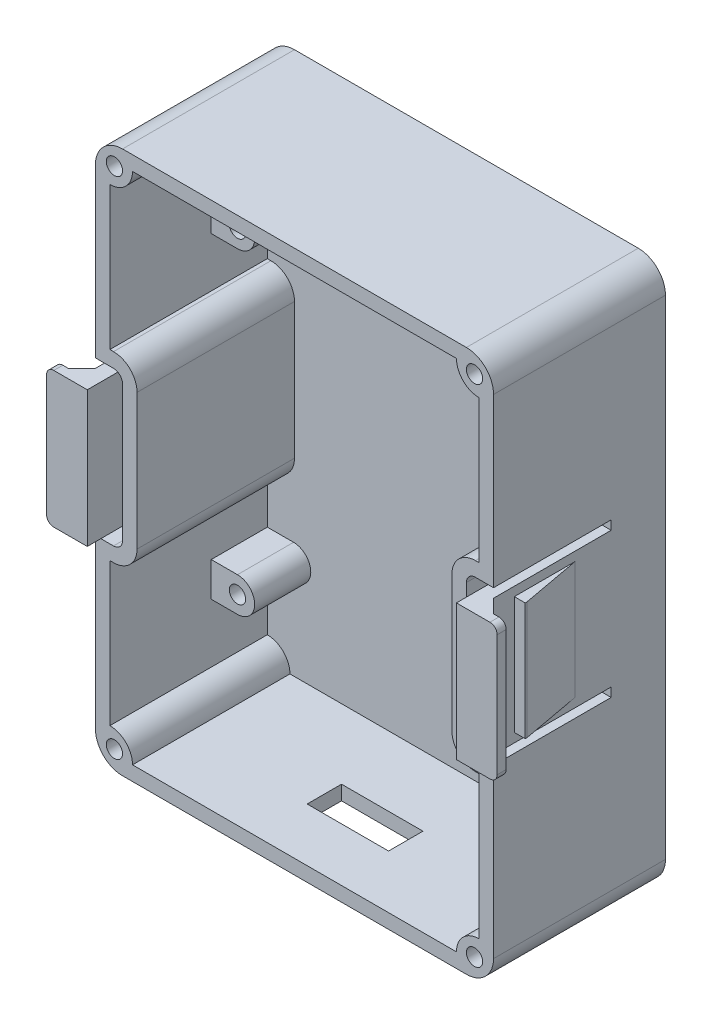
SolidWorks part; units mm, degrees
ref_plane "前视基准面" through (0, 0, 0) normal (0, 0, 1) x (1, 0, 0)
ref_plane "上视基准面" through (0, 0, 0) normal (0, 1, 0) x (1, 0, 0)
ref_plane "右视基准面" through (0, 0, 0) normal (1, 0, 0) x (0, 0, -1)
sketch "草图1" plane through (0, 0, 0) normal (0, 0, 1) x (1, 0, 0)
  line L1 (-22, -30) -> (22, -30)
  line L2 (-22, -30) -> (-22, 30)
  line L3 (-22, 30) -> (22, 30)
  line L4 (22, -30) -> (22, 30)
  line L5 (-22, -30) -> (22, 30) construction
  line L6 (-22, 30) -> (22, -30) construction
  point P0 (0, 0)
  dimension "D1" = 60
  dimension "D2" = 44
extrude "凸台-拉伸1" add sketch "草图1" along normal blind 19
sketch "草图2" plane through (0, 0, 19) normal (0, 0, 1) x (1, 0, 0)
  line L0 (-22, 30) -> (-22, -30) construction
  line L1 (-22, -8.5) -> (-19, -8.5)
  line L2 (-22, -8.5) -> (-22, 8.5)
  line L3 (-22, 8.5) -> (-19, 8.5)
  line L4 (-19, -8.5) -> (-19, 8.5)
  line L5 (-22, -30) -> (22, -30) construction
  line L6 (0, -10.45) -> (0, 10.45) construction
  line L7 (22, 8.5) -> (19, 8.5)
  line L8 (19, -8.5) -> (19, 8.5)
  line L9 (22, -8.5) -> (19, -8.5)
  line L10 (22, -8.5) -> (22, 8.5)
  point P8 (-19, 0)
  dimension "D1" = 21.5
  dimension "D2" = 3
extrude "切除-拉伸1" cut sketch "草图2" against normal through all
fillet "圆角1" radius 3 4 edges at (-22, 30, 9.5) (22, 30, 9.5) (22, -30, 9.5) (-22, -30, 9.5)
fillet "圆角2" radius 1 4 edges at (-19, 8.5, 9.5) (-19, -8.5, 9.5) (19, -8.5, 9.5) (19, 8.5, 9.5)
shell "抽壳1" thickness 1.6 removed face at (0, 0, 19)
sketch "草图3" plane through (0, 0, 1.6) normal (0, 0, 1) x (1, 0, 0)
  line L2 (-20.4, 28.4) -> (-17.9, 28.4)
  line L3 (-20.4, 28.4) -> (-20.4, 25.9)
  line L6 (-20.4, 27) -> (-20.4, 10.1) construction
  line L7 (19, 28.4) -> (-19, 28.4) construction
  arc A0 (-20.4, 25.9) -> (-17.9, 28.4) centre (-20.4, 28.4) ccw
  circle A1 centre (-19.9, 27.9) radius 0.9
  dimension "D1" = 2.5
  dimension "D2" = 1.8
  dimension "D3" = 0.5
  dimension "D4" = 0.5
extrude "凸台-拉伸2" add sketch "草图3" along normal up to surface (17.4 mm away) contours A0 L2 L3 up to face at (0, 0, 19)
extrude "切除-拉伸2" cut sketch "草图3<3>" along normal up to surface (17.4 mm away) contours A1 up to face at (0.0954, -0.0954, 19)
sketch "草图3<3>" plane through (0, 0, 1.6) normal (0, 0, 1) x (1, 0, 0) same geometry as "草图3"
mirror "镜向1" about plane through (0, 0, 0) normal (1, 0, 0) of "切除-拉伸2", "凸台-拉伸2"
mirror "镜向2" about plane through (0, 0, 0) normal (0, 1, 0) of "切除-拉伸2", "镜向1", "凸台-拉伸2"
sketch "草图4" plane through (0, 0, 1.6) normal (0, 0, 1) x (1, 0, 0)
  line L0 (22, -27) -> (22, -8.5) construction
  line L1 (18.5, -28.4) -> (13.5, -28.4)
  line L2 (18.5, -28.4) -> (18.5, -13.4)
  line L3 (18.5, -13.4) -> (13.5, -13.4)
  line L4 (13.5, -28.4) -> (13.5, -13.4)
  line L5 (15.1, -25.3) -> (16.9, -25.3)
  line L6 (15.1, -25.3) -> (15.1, -27)
  line L7 (15.1, -27) -> (16.9, -27)
  line L8 (16.9, -25.3) -> (16.9, -27)
  line L9 (-19, -30) -> (19, -30) construction
  line L10 (-19, -30) -> (19, -30) construction
  line L11 (15.1, -22.76) -> (15.1, -24.46)
  line L12 (15.1, -22.76) -> (16.9, -22.76)
  line L13 (16.9, -22.76) -> (16.9, -24.46)
  line L14 (15.1, -24.46) -> (16.9, -24.46)
  line L15 (15.1, -20.22) -> (15.1, -21.92)
  line L16 (15.1, -20.22) -> (16.9, -20.22)
  line L17 (16.9, -20.22) -> (16.9, -21.92)
  line L18 (15.1, -21.92) -> (16.9, -21.92)
  line L19 (15.1, -17.68) -> (15.1, -19.38)
  line L20 (15.1, -17.68) -> (16.9, -17.68)
  line L21 (16.9, -17.68) -> (16.9, -19.38)
  line L22 (15.1, -19.38) -> (16.9, -19.38)
  line L23 (15.1, -15.14) -> (15.1, -16.84)
  line L24 (15.1, -15.14) -> (16.9, -15.14)
  line L25 (16.9, -15.14) -> (16.9, -16.84)
  line L26 (15.1, -16.84) -> (16.9, -16.84)
  line L27 (-17.9, -28.4) -> (17.9, -28.4) construction
  point P32 (16, -15.14)
  point P33 (16, -13.4)
  dimension "D1" = 5.1
  dimension "D2" = 6.9
  dimension "D3" = 3
  dimension "D4" = 4.7
  dimension "D6" = 5
  dimension "D7" = 2.54
  dimension "D8" = 15
  dimension "D5" = 5
extrude "凸台-拉伸3" add sketch "草图4" along normal offset from surface (6.2 mm away) 7.8 contours L2 L3 L4 L1 up to face at (0, 0, 0)
extrude "切除-拉伸3" cut sketch "草图4<4>" against normal through all both and the other way through all contours L26 L25 L24 L23 | L22 L21 L20 L19 | L18 L17 L16 L15 | L14 L13 L12 L11 | L7 L8 L5 L6
sketch "草图4<4>" plane through (0, 0, 1.6) normal (0, 0, 1) x (1, 0, 0) same geometry as "草图4"
sketch "草图5" plane through (0, 0, 1.6) normal (0, 0, 1) x (1, 0, 0)
  line L1 (-17.5, 19.4) -> (-20.4, 19.4)
  line L2 (-20.4, 25.9) -> (-20.4, 10.1) construction
  line L3 (-20.4, 19.4) -> (-20.4, 15.6)
  line L4 (-20.4, 15.6) -> (-17.5, 15.6)
  line L5 (0, -10.45) -> (0, 10.45) construction
  line L6 (20.4, 15.6) -> (17.5, 15.6)
  line L7 (20.4, 19.4) -> (20.4, 15.6)
  line L8 (17.5, 19.4) -> (20.4, 19.4)
  line L9 (10.45, 0) -> (-10.45, 0) construction
  line L10 (-20.4, -15.6) -> (-17.5, -15.6)
  line L11 (-20.4, -19.4) -> (-20.4, -15.6)
  line L12 (-17.5, -19.4) -> (-20.4, -19.4)
  circle A0 centre (-17.5, 17.5) radius 0.9
  arc A2 (-17.5, 15.6) -> (-17.5, 19.4) centre (-17.5, 17.5) ccw
  circle A3 centre (17.5, 17.5) radius 0.9
  arc A4 (17.5, 15.6) -> (17.5, 19.4) centre (17.5, 17.5) cw
  circle A5 centre (-17.5, -17.5) radius 0.9
  arc A6 (-17.5, -15.6) -> (-17.5, -19.4) centre (-17.5, -17.5) cw
  dimension "D1" = 1.8
  dimension "D2" = 3.8
  dimension "D3" = 35
  dimension "D4" = 35
extrude "凸台-拉伸4" add sketch "草图5" along normal up to surface (6.2 mm away) up to face at (16, -15.99, 7.8)
sketch "草图6" plane through (0, -28.4, 0) normal (0, 1, 0) x (1, 0, 0)
  line L0 (13.5, -7.8) -> (17.9, -7.8) construction
  line L3 (-4.5, -13.1) -> (4.5, -13.1)
  line L4 (-4.5, -13.1) -> (-4.5, -9.3)
  line L5 (-4.5, -9.3) -> (4.5, -9.3)
  line L6 (4.5, -13.1) -> (4.5, -9.3)
  point P4 (0, -13.1)
  dimension "D1" = 9
  dimension "D2" = 3.8
  dimension "D3" = 1.5
extrude "切除-拉伸4" cut sketch "草图6" against normal through all
sketch "草图8" plane through (0, 0, 0) normal (0, 0, -1) x (-1, 0, 0)
  line L0 (-19, 7.5) -> (-19, -7.5) construction
  line L1 (-22, 8.5) -> (-19, 8.5)
  line L2 (-22, 8.5) -> (-22, -8.5)
  line L3 (-22, -8.5) -> (-19, -8.5)
  line L4 (-19, 8.5) -> (-19, -8.5)
  line L5 (-22, 8.5) -> (-22, 27) construction
  line L6 (-22, 8.5) -> (-20, 8.5) construction
  line L7 (-20, -8.5) -> (-22, -8.5) construction
extrude "凸台-拉伸5" add sketch "草图8" against normal blind 6
sketch "草图9" plane through (0, 0, 6) normal (0, 0, 1) x (1, 0, 0)
  line L0 (22, 8.5) -> (22, -8.5) construction
  line L1 (22, 7.5) -> (20.4, 7.5)
  line L2 (22, 7.5) -> (22, -7.5)
  line L3 (22, -7.5) -> (20.4, -7.5)
  line L4 (20.4, 7.5) -> (20.4, -7.5)
  line L5 (19, -7.5) -> (19, 7.5) construction
  point P6 (22, 0)
  point P7 (22, 0)
  dimension "D1" = 15
  dimension "D2" = 1.4
extrude "凸台-拉伸6" add sketch "草图9" along normal offset from surface (15.5 mm away) 21.5 up to face at (-8.6847, 0, 0)
sketch "草图10" plane through (0, -7.5, 0) normal (0, -1, 0) x (1, 0, 0)
  line L0 (22, 21.5) -> (24.9, 21.5)
  line L1 (24.9, 21.5) -> (24.9, 20.5)
  line L2 (24.9, 20.5) -> (23.5, 20.5)
  line L3 (23.5, 20.5) -> (22, 19)
  line L4 (22, 21.5) -> (22, 6) construction
  line L5 (22, 19) -> (22, 0) construction
  line L6 (22, 19) -> (22, 21.5)
  line L7 (20.4, 21.5) -> (20.4, 6) construction
  line L8 (20.8, 19) -> (19, 19) construction
  point P3 (24.9, 21)
  dimension "D1" = 1
  dimension "D2" = 4.5
  dimension "D3" = 45
extrude "凸台-拉伸7" add sketch "草图10" against normal up to surface (15 mm away) up to face at (21.2, 7.5, 13.75)
sketch "草图11" plane through (0, 0, 0) normal (0, 1, 0) x (1, 0, 0)
  line L0 (23.2, -16.5) -> (22, -10)
  line L1 (22, -19) -> (22, -6) construction
  line L3 (22, -16.7) -> (22, -10)
  line L4 (-19, 0) -> (19, 0) construction
  line L5 (23.2, -16.5) -> (23.2, -16.7)
  line L6 (23.2, -16.7) -> (22, -16.7)
  line L7 (19, 0) -> (-19, 0) construction
  dimension "D1" = 1.2
  dimension "D2" = 10
  dimension "D3" = 16.7
  dimension "D4" = 0.2
extrude "凸台-拉伸8" add sketch "草图11" along normal mid plane 13
fillet "圆角3" radius 0.8 2 edges at (24.9, -7.5, 21) (24.9, 7.5, 21)
mirror "镜向3" about plane through (0, 0, 0) normal (1, 0, 0) of "凸台-拉伸6", "凸台-拉伸7", "凸台-拉伸8", "圆角3", "凸台-拉伸5"
